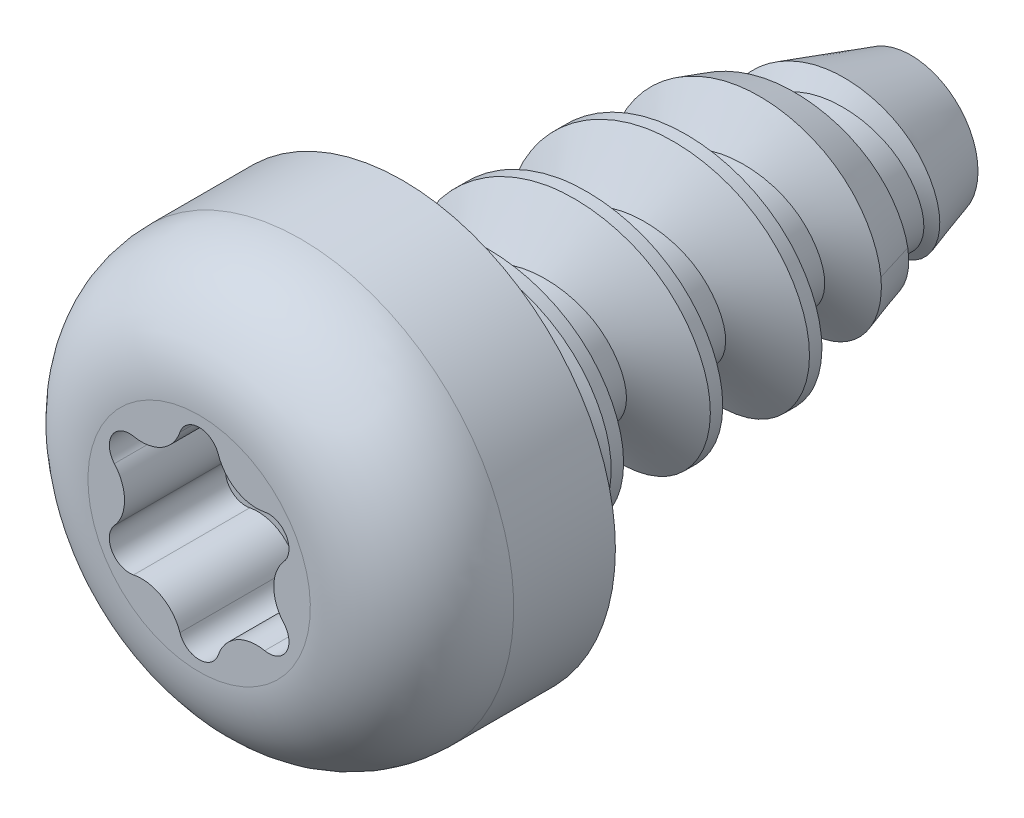
SolidWorks part; units mm, degrees
ref_plane "Front" through (0, 0, 0) normal (0, 0, 1) x (1, 0, 0)
ref_plane "Top" through (0, 0, 0) normal (0, 1, 0) x (1, 0, 0)
ref_plane "Right" through (0, 0, 0) normal (1, 0, 0) x (0, 0, -1)
sketch "Sketch1" plane through (0, 0, 0) normal (0, 0, 1) x (1, 0, 0)
  circle A0 centre (0, 0) radius 1.675
  dimension "Head Dia" = 3.35
extrude "Extrude3" add sketch "Sketch1" along normal blind 1.6
ref_plane "Plane1" through (0, 0, 1.6) normal (0, 0, 1) x (1, 0, 0)
sketch "Sketch11" plane through (0, 0, 0) normal (1, 0, 0) x (0, 0, -1)
  line L2 (-1.6, 1.675) -> (-1.6, -1.675) construction
  line L4 (0, 1.675) -> (-1.6, 1.675) construction
  line L5 (-0.8, 1.675) -> (-0.8, 1.775)
  line L6 (-0.8, 1.775) -> (-1.7, 1.775)
  line L7 (-1.7, 1.775) -> (-1.7, 0.875)
  line L8 (-1.7, 0.875) -> (-1.6, 0.875)
  line L11 (0, 0) -> (-1.6, 0) construction
  arc A0 (-1.6, 0.875) -> (-0.8, 1.675) centre (-0.8, 0.875) cw
  dimension "D1" = 0.1
  dimension "D2" = 0.1
revolve "Cut-Revolve3" cut sketch "Sketch11" angle 360 about L11
sketch "Sketch14" plane through (0, 0, 0) normal (1, 0, 0) x (0, 0, -1)
  line L0 (0.195, 0.5778) -> (0.4388, 1) construction
  line L2 (0.4388, 1) -> (0.5363, 1)
  line L3 (0.5363, 1) -> (0.78, 0.5778) construction
  line L4 (0.78, 0.5778) -> (0.195, 0.5778) construction
  line L5 (0.78, 0.5778) -> (0.975, 0.5778) construction
  line L6 (0.195, 0.5778) -> (0, 0.5778) construction
  line L10 (0, 1.675) -> (0, -1.675) construction
  line L11 (0.4388, 1) -> (0.195, 0.5778)
  line L12 (0.195, 0.5778) -> (0.78, 0.5778)
  line L13 (0.78, 0.5778) -> (0.5363, 1)
  line L14 (0, 0) -> (-1.6, 0) construction
  line L15 (0, 0) -> (-1.6, 0) construction
  point P11 (0.4875, 1)
  dimension "D1" = 60
  dimension "Pitch" = 0.78
  dimension "D3" = 0.195
  dimension "D4" = 0.0975
  dimension "Screw Dia" = 2
ref_plane "Plane2" through (0, 0, -0.4875) normal (0, 0, 1) x (1, 0, 0)
sketch "Sketch4" plane through (0, 0, 0) normal (1, 0, 0) x (0, 0, -1)
  line L0 (0, 0) -> (4, 0)
  line L2 (4, -0.5778) -> (0, -0.5778) construction
  line L3 (4, 0) -> (4, 0.5778)
  line L4 (4, 0.5778) -> (0, 0.5778)
  line L5 (0, 0) -> (-1.6, 0) construction
  line L6 (0, 0.5778) -> (0, 0)
  line L7 (4, 0) -> (6.54, 0) construction
  line L8 (0.195, 0.5778) -> (0.78, 0.5778) construction
  point P7 (0, 0.5778)
  dimension "D1" = 2.54
  dimension "Body Length" = 4
revolve "Revolve1" add sketch "Sketch4" angle 360 about L7
sketch "Sketch15" plane through (0, 0, -0.4875) normal (0, 0, 1) x (1, 0, 0)
  circle A0 centre (0, 0) radius 1
curve "Helix/Spiral1" pitch 0.78 height 1.17 radius 1 centre (0, 0, -0.4875) axis (0, 0, -1) start towards (0, 1, 0)
sweep "Sweep1" add profiles "Sketch14" path "Helix/Spiral1"
pattern_linear "LPattern3" count 5 spacing 0.78 along (0, 0, -1) count 2 spacing 0.78 along (0, 0, 1) of "Sweep1"
sketch "Sketch13" plane through (0, 0, 0) normal (1, 0, 0) x (0, 0, -1)
  line L0 (4, 0.5278) -> (2.4649, 1)
  line L2 (2.4649, 1) -> (4, 1)
  line L3 (4, 1) -> (4, 0.5278) construction
  line L4 (4, 0.5278) -> (4, 0)
  line L5 (0, 0) -> (4, 0) construction
  line L6 (0.4388, 1) -> (0.5363, 1) construction
  line L7 (5.56, 0) -> (5.56, 1)
  line L8 (5.56, 1) -> (4, 1)
  line L9 (4, 0) -> (5.56, 0)
  dimension "D1" = 17.097
  dimension "D2" = 0.05
  dimension "D3" = 1.56
revolve "Cut-Revolve4" cut sketch "Sketch13" angle 360 about L5
sketch "Sketch12" plane through (0, 0, 1.6) normal (0, 0, 1) x (1, 0, 0)
  line L0 (0, 0) -> (0, 0.7914) construction
  line L1 (-0.2935, 0.5084) -> (0, 0)
  line L2 (0, 0) -> (0.2935, 0.5084)
  arc A0 (-0.2935, 0.5084) -> (-0.1509, 0.6829) centre (-0.4526, 0.784) ccw
  arc A1 (-0.1509, 0.6829) -> (0.1509, 0.6829) centre (0, 0.6323) cw
  arc A2 (0.1509, 0.6829) -> (0.2935, 0.5084) centre (0.4526, 0.784) ccw
  circle A5 centre (0, 0) radius 0.7914 construction
  dimension "D1" = 60
  dimension "M" = 1.5829
  dimension "D2" = 0.1591
  dimension "D3" = 0.3183
ref_axis "Axis1" through (0, 0, 1.6) along (0, 0, -1)
extrude "Cut-Extrude1" cut sketch "Sketch12" against normal blind 0.9143
pattern_circular "CirPattern1" count 6 every 60 about axis through (0, 0, 1.6) along (0, 0, -1) of "Cut-Extrude1"
equation "\"D3@LPattern3\"=\"Pitch@Sketch14\""
equation "\"D1@LPattern3\"=(\"Body Length@Sketch4\"/\"Pitch@Sketch14\")"
equation "\"D1@Cut-Extrude1\"=\"Head Ht@Extrude3\"*2/3.5"
equation "\"D3@Sketch14\" = \"Pitch@Sketch14\"/4"
equation "\"D4@Sketch14\" = \"Pitch@Sketch14\"/8"
equation "\"D4@LPattern3\" = \"D3@LPattern3\""
equation "\"D4@Helix/Spiral1\" = \"Pitch@Sketch14\""
equation "\"D2@Sketch12\" = \"Head Dia@Sketch1\" * .0475"
equation "\"D3@Sketch12\" = \"Head Dia@Sketch1\" * .095"
equation "\"M@Sketch12\" = \"Head Dia@Sketch1\" * 0.4725"
equation "\"D3@Sketch13\" = \"D4@Helix/Spiral1\" * 2"
